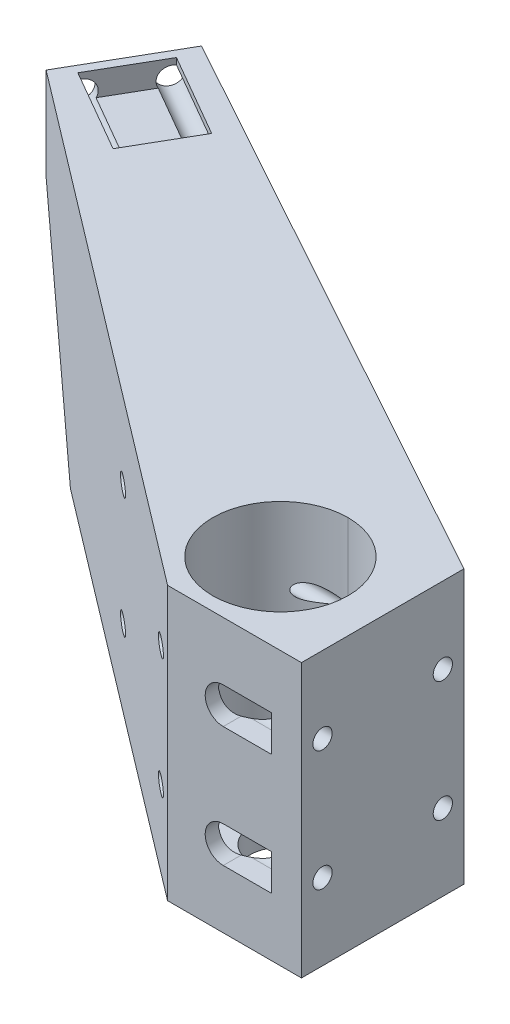
SolidWorks part; units mm, degrees
ref_plane "Front" through (0, 0, 0) normal (0, 0, 1) x (1, 0, 0)
ref_plane "Top" through (0, 0, 0) normal (0, 1, 0) x (1, 0, 0)
ref_plane "Right" through (0, 0, 0) normal (1, 0, 0) x (0, 0, -1)
sketch "Sketch2" plane through (0, 0, 0) normal (0, 1, 0) x (1, 0, 0)
  line L0 (0, 0) -> (-17, 0) construction
  line L2 (-44, 25.4034) -> (-44, 0) construction
  line L3 (-44, 0) -> (-17, 0) construction
  line L4 (0, 0) -> (-44, 25.4034) construction
  circle A0 centre (-17, 0) radius 11.25
  circle A2 centre (-44, 25.4034) radius 5 construction
  dimension "D3" = 22.5
  dimension "D7" = 10
  dimension "D1" = 27
  dimension "D2" = 25.4034
  dimension "D5" = 17
  dimension "D6" = 30
sketch "Sketch3" plane through (0, 0, 0) normal (0, 1, 0) x (1, 0, 0)
  line L0 (0, -13.5) -> (0, 13.5)
  line L1 (-94, 54.27) -> (0, 0) construction
  line L2 (-101.7943, 58.7699) -> (-86.2057, 49.7701) construction
  line L8 (-22.2548, -13.5) -> (0, -13.5)
  line L9 (-106.5228, 50.5797) -> (-97.0657, 66.9602)
  line L10 (0, 13.5) -> (-97.0657, 66.9602)
  line L11 (-22.2548, -13.5) -> (-106.5228, 50.5797)
  point P3 (0, 0)
  point P4 (0, 0)
  point P11 (-94, 54.27)
  point P16 (-94, 54.27)
  point P19 (-101.7943, 58.7699)
  dimension "D1" = 27
  dimension "D3" = 54.27
  dimension "D4" = 94
  dimension "D5" = 97.251
  dimension "D6" = 18
  dimension "D7" = 91.155
extrude "Boss-Extrude1" add sketch "Sketch3" against normal blind 45.4
sketch "Sketch4" plane through (0, 0, 0) normal (0, -1, 0) x (-1, 0, 0)
  line L0 (17, 11.25) -> (5.75, 11.25)
  line L1 (5.75, 11.25) -> (5.75, 0)
  line L2 (0, 0) -> (17, 0) construction
  line L3 (5.75, 0) -> (5.75, -11.25)
  line L4 (5.75, -11.25) -> (17, -11.25)
  circle A0 centre (17, 0) radius 11.25 construction
  arc A2 (17, 11.25) -> (17, -11.25) centre (17, 0) cw
extrude "Cut-Extrude2" cut sketch "Sketch4" along normal offset from surface (41.4 mm away) 4 up to face at (-45.1687, -45.4, -20.808)
ref_plane "Plane1" through (-100.4952, 0, -58.02) normal (-0.866, 0, -0.5) x (-0.5, 0, 0.866)
sketch "Sketch5" plane through (-1127.2277, 0, 1717.3632) normal (0.866, 0, 0.5) x (0.5, 0, -0.866)
  line L0 (2050.8931, 0) -> (2050.8931, -3) construction
  line L2 (2050.8931, -3) -> (2056.4092, -3) construction
  line L3 (2050.8931, 1.3096) -> (2050.8931, 0) construction
  line L4 (2056.4092, -3) -> (2050.8931, 1.3096) construction
  line L6 (2060.3504, 0) -> (2041.4359, 0) construction
  circle A0 centre (2056.4092, -3) radius 2
  circle A1 centre (2045.377, -3) radius 2
  circle A2 centre (2050.8931, 1.3096) radius 5 construction
  point P16 (2050.8931, 0)
  dimension "D1" = 4
  dimension "D2" = 10
  dimension "D3" = 38
  dimension "D4" = 3
extrude "Cut-Extrude3" cut sketch "Sketch5" along normal blind 20
sketch "Sketch6" plane through (-100.4952, 0, -58.02) normal (-0.866, 0, -0.5) x (-0.5, 0, 0.866)
  line L5 (-6, 0) -> (6, 0)
  line L6 (-6, 0) -> (-6, -4)
  line L7 (-6, -4) -> (6, -4)
  line L8 (6, 0) -> (6, -4)
  line L9 (-9.4573, 0) -> (9.4573, 0) construction
  point P4 (0, 0)
  point P8 (0, 0)
  dimension "D1" = 4
  dimension "D2" = 12
extrude "Cut-Extrude4" cut sketch "Sketch6" against normal blind 16
chamfer "Chamfer1" distance 30 angle 35 1 edges at (-101.7943, -45.4, -58.7699)
sketch "Sketch7" plane through (-5.75, 0, 0) normal (-1, 0, 0) x (0, 0, 1)
  line L0 (0, -22.7) -> (0, 0) construction
  line L1 (-10, -32.7) -> (10, -32.7) construction
  line L2 (-10, -32.7) -> (-10, -12.7) construction
  line L3 (-10, -12.7) -> (10, -12.7) construction
  line L4 (10, -32.7) -> (10, -12.7) construction
  line L5 (-10, -32.7) -> (10, -12.7) construction
  line L6 (-10, -12.7) -> (10, -32.7) construction
  line L7 (0, -22.7) -> (0, -45.4) construction
  line L8 (13.5, -45.4) -> (-13.5, -45.4) construction
  circle A0 centre (10, -12.7) radius 1.6
  circle A1 centre (-10, -12.7) radius 1.6
  circle A2 centre (10, -32.7) radius 1.6
  circle A3 centre (-10, -32.7) radius 1.6
  point P4 (0, -22.7)
  dimension "D1" = 20
  dimension "D3" = 3.2
  dimension "D2" = 20
extrude "Cut-Extrude5" cut sketch "Sketch7" against normal through all
sketch "Sketch8" plane through (0, 0, 13.5) normal (0, 0, 1) x (1, 0, 0)
  line L0 (-5, -15.7) -> (-5, -9.7)
  line L3 (-5, -9.7) -> (-13, -9.7)
  line L4 (-5, -12.7) -> (-13, -12.7) construction
  line L5 (-5, -15.7) -> (-13, -15.7)
  line L6 (-5, -32.7) -> (-13, -32.7) construction
  line L8 (-5, -29.7) -> (-5, -35.7)
  line L10 (-5, -29.7) -> (-13, -29.7)
  line L11 (-5, -35.7) -> (-13, -35.7)
  line L12 (0, -45.4) -> (0, 0) construction
  line L13 (0, -11.1) -> (0, -14.3) construction
  line L14 (-5.75, -14.3) -> (0, -14.3) construction
  line L15 (0, -12.7) -> (-5, -12.7) construction
  line L16 (0, -31.1) -> (0, -34.3) construction
  line L17 (0, -32.7) -> (-5, -32.7) construction
  arc A0 (-13, -9.7) -> (-13, -15.7) centre (-13, -12.7) ccw
  arc A1 (-13, -29.7) -> (-13, -35.7) centre (-13, -32.7) ccw
  dimension "D2" = 6
  dimension "D3" = 5
  dimension "D1" = 8
extrude "Cut-Extrude6" cut sketch "Sketch8" against normal through all
ref_plane "Plane2" through (-106.5228, 0, 0) normal (1, 0, 0) x (0, 0, -1)
fillet "Fillet3" radius 11.25 2 edges at (-5.75, -4.85, 11.25) (-5.75, -4.85, -11.25)
sketch "Sketch9" plane through (-106.5228, 0, 0) normal (1, 0, 0) x (0, 0, -1)
  circle A0 centre (10, -12.7) radius 1.3
  circle A1 centre (10, -32.7) radius 1.3
  circle A2 centre (-10, -12.7) radius 1.3
  circle A3 centre (-10, -32.7) radius 1.3
  dimension "D1" = 2.6
extrude "Cut-Extrude7" cut sketch "Sketch9" along normal up to surface (106.5228 mm away)
ref_plane "Plane3" through (0, 0, 0) normal (0.5, 0, -0.866) x (-0.866, 0, -0.5)
ref_plane "Plane4" through (-0.75, 0, 1.299) normal (0.5, 0, -0.866) x (-0.866, 0, -0.5)
sketch "Sketch11" plane through (0, -45.4, 0) normal (0, -1, 0) x (1, 0, 0)
  line L0 (-17, 0) -> (-17, 8) construction
  line L1 (-44, 0) -> (-17, 0) construction
  circle A0 centre (-17, 0) radius 5
  circle A1 centre (-17, 8) radius 1.6
  circle A2 centre (-9, 0) radius 1.6
  circle A3 centre (-17, -8) radius 1.6
  circle A4 centre (-25, 0) radius 1.6
  point P14 (-17, 0)
  dimension "D1" = 10
  dimension "D2" = 3.2
  dimension "D3" = 8
  dimension "D4" = 4
extrude "Cut-Extrude8" cut sketch "Sketch11" against normal through all
chamfer "Chamfer4" [suppressed] distance 3 angle 45
chamfer "Chamfer5" [suppressed] distance 3 angle 45
sketch "Sketch13"
  point P0 (7593866.6537, 7148790.7028)
extrude "Cut-Extrude10" [suppressed] cut sketch "Sketch13" against normal blind 7
sketch "Sketch26" plane through (-74.5712, -60.2928, -43.053) normal (-0.7094, -0.5736, -0.4096) x (-0.3185, -0.2575, 0.9123)
  line L0 (-26.206, 49.0527) -> (-8.2504, 54.9987) construction
  line L1 (-17.2282, 52.0257) -> (-2.4691, 18.3341) construction
  line L2 (5.7996, 21.0722) -> (-15.0953, 14.1529) construction
  circle A1 centre (-14.8207, 46.5299) radius 2.55
  dimension "D1" = 5.1
  dimension "D2" = 6
extrude "Cut-Extrude18" cut sketch "Sketch26" against normal blind 6 draft 3
chamfer "Chamfer6" [suppressed] distance 0.2 angle 60
sketch "Sketch25" plane through (-5, 0, 0) normal (-1, 0, 0) x (0, 0, 1)
  line L0 (10, -9.7) -> (-10, -9.7)
  line L1 (-10, -15.7) -> (10, -15.7)
  line L2 (10, -29.7) -> (-10, -29.7)
  line L3 (-10, -35.7) -> (10, -35.7)
  circle A0 centre (-10, -12.7) radius 3 construction
  circle A1 centre (10, -12.7) radius 3 construction
  circle A2 centre (-10, -32.7) radius 3 construction
  circle A3 centre (10, -32.7) radius 3 construction
  arc A4 (-10, -29.7) -> (-10, -35.7) centre (-10, -32.7) cw
  arc A5 (10, -29.7) -> (10, -35.7) centre (10, -32.7) ccw
  arc A6 (10, -9.7) -> (10, -15.7) centre (10, -12.7) ccw
  arc A7 (-10, -9.7) -> (-10, -15.7) centre (-10, -12.7) cw
  dimension "D1" = 6
extrude "Boss-Extrude10" add sketch "Sketch25" along normal up to surface (6.8461 mm away)
mirror "Mirror3" [suppressed]
delete or keep bodies "Body-Delete/Keep 1" [suppressed] type delete bodies bodies 129
sketch "Sketch14" plane through (0, 0, 0) normal (0, 1, 0) x (1, 0, 0)
  line L0 (0, -13.5) -> (0, 13.5)
  line L1 (0, -13.5) -> (-22.2548, -13.5)
  line L3 (1.4582, -36.428) -> (26.7129, 7.3151)
  line L4 (26.7129, 7.3151) -> (-1, 23.3149)
  line L8 (0, 13.5) -> (-5, 16.3867)
  line L9 (-5, 16.3867) -> (-1, 23.3149)
  line L10 (-22.2548, -13.5) -> (-26.2547, -20.4282)
  line L11 (-26.2547, -20.4282) -> (1.4582, -36.428)
  line L12 (-103.5523, 55.7249) -> (-105.5523, 52.2608) construction
  dimension "D1" = 8
  dimension "D2" = 32
extrude "Boss-Extrude3" [suppressed] add sketch "Sketch14" against normal up to surface (34.7 mm away) separate body
delete or keep bodies "Body-Delete/Keep 2" [suppressed] type keep bodies bodies 116
ref_plane "Plane6" [suppressed] through (3.9225, 3.1715, 2.2647) normal (-0.7094, -0.5736, -0.4096) x (-0.3185, -0.2575, 0.9123)
ref_plane "Plane7" [suppressed] through (6.7601, 5.4658, 3.903) normal (-0.7094, -0.5736, -0.4096) x (-0.3185, -0.2575, 0.9123)
sketch "Sketch15" [suppressed] plane through (6.7601, 5.4658, 3.903) normal (-0.7094, -0.5736, -0.4096) x (-0.3185, -0.2575, 0.9123)
  line L1 (-19.0792, 20.424) -> (20.9208, 20.424)
  line L2 (-19.0792, 20.424) -> (-19.0792, -19.576)
  line L3 (-19.0792, -19.576) -> (20.9208, -19.576)
  line L4 (20.9208, 20.424) -> (20.9208, -19.576)
  circle A0 centre (-4.1074, 12.4032) radius 1.3 construction
  circle A1 centre (-4.1074, 12.4032) radius 1.3
  dimension "D1" = 40
  dimension "D2" = 40
extrude "Boss-Extrude6" [suppressed] add sketch "Sketch15" along normal up to surface (45.7848 mm away) separate body contours L2 L1 L4 L3
sketch "Sketch16" [suppressed] plane through (6.7601, 5.4658, 3.903) normal (0.7094, 0.5736, 0.4096) x (0.3185, 0.2575, -0.9123)
  line L0 (19.0792, 20.424) -> (19.0792, -19.576) construction
  line L1 (19.0792, 20.424) -> (19.0792, -19.576)
  line L2 (19.0792, 20.424) -> (-20.9208, 20.424) construction
  line L3 (-20.9208, 20.424) -> (-20.9208, -19.576) construction
  line L4 (19.0792, -19.576) -> (-20.9208, -19.576) construction
  line L5 (19.0792, 20.424) -> (-20.9208, 20.424)
  line L6 (-20.9208, 20.424) -> (-20.9208, -19.576)
  line L7 (19.0792, -19.576) -> (-20.9208, -19.576)
extrude "Boss-Extrude8" [suppressed] add sketch "Sketch16" against normal up to surface (35.4449 mm away)
sketch "Sketch17" [suppressed] plane through (6.7601, 5.4658, 3.903) normal (0.7094, 0.5736, 0.4096) x (0.3185, 0.2575, -0.9123)
  line L4 (-20.9208, -19.576) -> (19.0792, -19.576)
  line L5 (19.0792, -19.576) -> (19.0792, 20.424)
  line L6 (19.0792, 20.424) -> (-20.9208, 20.424)
  line L7 (-20.9208, 20.424) -> (-20.9208, -19.576)
  line L8 (-20.9208, -19.576) -> (19.0792, -19.576)
  line L9 (19.0792, -19.576) -> (19.0792, 20.424)
  line L10 (19.0792, 20.424) -> (-20.9208, 20.424)
  line L11 (-20.9208, 20.424) -> (-20.9208, -19.576)
  dimension "D1" = 0
extrude "Boss-Extrude9" [suppressed] add sketch "Sketch17" against normal up to surface
sketch "Sketch18" [suppressed] plane through (6.7601, 5.4658, 3.903) normal (0.7094, 0.5736, 0.4096) x (0.3185, 0.2575, -0.9123)
  line L0 (-20.9208, 20.424) -> (-13.5615, 20.424)
  line L1 (19.0792, 20.424) -> (-20.9208, 20.424) construction
  line L2 (-5.0573, 27.3796) -> (-19.9959, 15.1613) construction
  line L3 (-13.5615, 20.424) -> (-19.9959, 15.1613)
  line L4 (-19.9959, 15.1613) -> (-20.9208, 12.3685)
  line L5 (-20.9208, 20.424) -> (-20.9208, -19.576) construction
  line L6 (-28.9317, -11.8222) -> (-19.9959, 15.1613) construction
  line L7 (-20.9208, 12.3685) -> (-20.9208, 20.424)
extrude "Cut-Extrude11" [suppressed] cut sketch "Sketch18" against normal through all
sketch "Sketch19" [suppressed] plane through (6.7601, 5.4658, 3.903) normal (0.7094, 0.5736, 0.4096) x (0.3185, 0.2575, -0.9123)
  line L0 (19.0792, 20.424) -> (5.833, -19.576)
  line L1 (19.0792, -19.576) -> (-20.9208, -19.576) construction
  line L2 (3.38, -26.9835) -> (12.3157, 0) construction
  line L3 (5.833, -19.576) -> (19.0792, -19.576)
  line L4 (19.0792, -19.576) -> (19.0792, 20.424)
extrude "Cut-Extrude12" [suppressed] cut sketch "Sketch19" against normal through all
delete or keep bodies "Body-Delete/Keep 3" [suppressed] type keep bodies bodies 121
ref_plane "Plane8" [suppressed] through (-25.7199, -20.7953, -14.8494) normal (0.7094, 0.5736, 0.4096) x (0.3185, 0.2575, -0.9123)
sketch "Sketch20" [suppressed] plane through (-25.7199, -20.7953, -14.8494) normal (0.7094, 0.5736, 0.4096) x (0.3185, 0.2575, -0.9123)
  line L0 (19.0792, 20.424) -> (-20.9208, 20.424) construction
  line L1 (-20.9208, 20.424) -> (-20.9208, -19.576) construction
  line L2 (19.0792, 20.424) -> (19.0792, -19.576) construction
  line L3 (19.0792, -19.576) -> (-20.9208, -19.576) construction
  line L4 (19.0792, 20.424) -> (-20.9208, 20.424)
  line L5 (-20.9208, 20.424) -> (-20.9208, -19.576)
  line L6 (19.0792, 20.424) -> (19.0792, -19.576)
  line L7 (19.0792, -19.576) -> (-20.9208, -19.576)
extrude "Cut-Extrude13" [suppressed] cut sketch "Sketch20" along normal up to vertex
sketch "Sketch21" [suppressed] plane through (6.7601, 5.4658, 3.903) normal (0.7094, 0.5736, 0.4096) x (0.3185, 0.2575, -0.9123)
  line L0 (-20.9208, 20.424) -> (-20.9208, -19.576) construction
  line L1 (19.0792, 20.424) -> (-20.9208, 20.424) construction
  line L2 (19.0792, -19.576) -> (-20.9208, -19.576) construction
  line L3 (19.0792, 20.424) -> (19.0792, -19.576) construction
  line L4 (-20.9208, 20.424) -> (-20.9208, -19.576)
  line L5 (19.0792, 20.424) -> (-20.9208, 20.424)
  line L6 (19.0792, -19.576) -> (-20.9208, -19.576)
  line L7 (19.0792, 20.424) -> (19.0792, -19.576)
extrude "Cut-Extrude14" [suppressed] cut sketch "Sketch21" against normal blind 3
mirror "Mirror4" [suppressed]
ref_plane "Plane9" [suppressed] through (-8.2131, -6.6405, -4.7418) normal (-0.7094, -0.5736, -0.4096) x (-0.3185, -0.2575, 0.9123)
sketch "Sketch22" [suppressed] plane through (-8.2131, -6.6405, -4.7418) normal (-0.7094, -0.5736, -0.4096) x (-0.3185, -0.2575, 0.9123)
  line L0 (-46.8746, -5.4638) -> (-45.2685, 0.9422) construction
  line L1 (-47.29, -7.1208) -> (-46.8746, -5.4638) construction
  line L2 (-46.3652, -9.9135) -> (-47.29, -7.1208) construction
  line L3 (-27.2989, -35.5442) -> (-46.3652, -9.9135) construction
  line L4 (-25.5961, -34.2774) -> (-27.2989, -35.5442) construction
  line L5 (-17.1478, -27.9929) -> (-25.5961, -34.2774) construction
  line L6 (-17.1478, -27.9929) -> (-5.833, -19.576) construction
  line L7 (8.269, -19.576) -> (-5.833, -19.576) construction
  line L8 (8.269, -19.576) -> (18.7984, -19.576) construction
  line L9 (18.7984, -19.576) -> (20.9208, -19.576) construction
  line L10 (-19.0792, 20.424) -> (-45.2685, 0.9422) construction
  line L11 (20.9208, -19.576) -> (20.9208, 12.3685) construction
  line L12 (20.9208, 12.3685) -> (19.9959, 15.1613) construction
  line L13 (19.9959, 15.1613) -> (18.6736, 16.2428) construction
  line L14 (-19.0792, 20.424) -> (13.5615, 20.424) construction
  line L15 (18.6736, 16.2428) -> (13.5615, 20.424) construction
  line L16 (-46.8746, -5.4638) -> (-45.2685, 0.9422)
  line L17 (-47.29, -7.1208) -> (-46.8746, -5.4638)
  line L18 (-46.3652, -9.9135) -> (-47.29, -7.1208)
  line L19 (-27.2989, -35.5442) -> (-46.3652, -9.9135)
  line L20 (-25.5961, -34.2774) -> (-27.2989, -35.5442)
  line L21 (-17.1478, -27.9929) -> (-25.5961, -34.2774)
  line L22 (-17.1478, -27.9929) -> (-5.833, -19.576)
  line L23 (8.269, -19.576) -> (-5.833, -19.576)
  line L24 (8.269, -19.576) -> (18.7984, -19.576)
  line L25 (18.7984, -19.576) -> (20.9208, -19.576)
  line L26 (-19.0792, 20.424) -> (-45.2685, 0.9422)
  line L27 (20.9208, -19.576) -> (20.9208, 12.3685)
  line L28 (20.9208, 12.3685) -> (19.9959, 15.1613)
  line L29 (19.9959, 15.1613) -> (18.6736, 16.2428)
  line L30 (-19.0792, 20.424) -> (13.5615, 20.424)
  line L31 (18.6736, 16.2428) -> (13.5615, 20.424)
extrude "Cut-Extrude15" [suppressed] cut sketch "Sketch22" against normal up to surface (2.0599 mm away)
sketch "Sketch23" [suppressed] plane through (0, -34.7, 0) normal (0, -1, 0) x (1, 0, 0)
  line L0 (34.8817, 6.8116) -> (17.3661, -23.5263) construction
  line L1 (44.7896, -4.9961) -> (29.2695, 13.5) construction
  line L2 (0, -13.5) -> (29.7829, -30.6952) construction
  line L3 (44.9403, -11.7664) -> (34.4546, -29.9283) construction
  text T0 "LBC-02" font "Century Gothic" height in points 20
  dimension "D1" = 18
extrude "Cut-Extrude16" [suppressed] cut sketch "Sketch23" against normal blind 0.4
sketch "Sketch24" plane through (0, -45.4, 0) normal (0, -1, 0) x (1, 0, 0)
  line L0 (-18.1388, -23.4902) -> (-33.7128, 4.787) construction
  line L2 (-89.6671, -37.7621) -> (-22.2548, 13.5) construction
  line L4 (0, -13.5) -> (-78.6619, -56.8241) construction
  text T0 "RBC-04" font "Century Gothic" height in points 20
  dimension "D1" = 27
extrude "Cut-Extrude17" cut sketch "Sketch24" against normal blind 0.4
